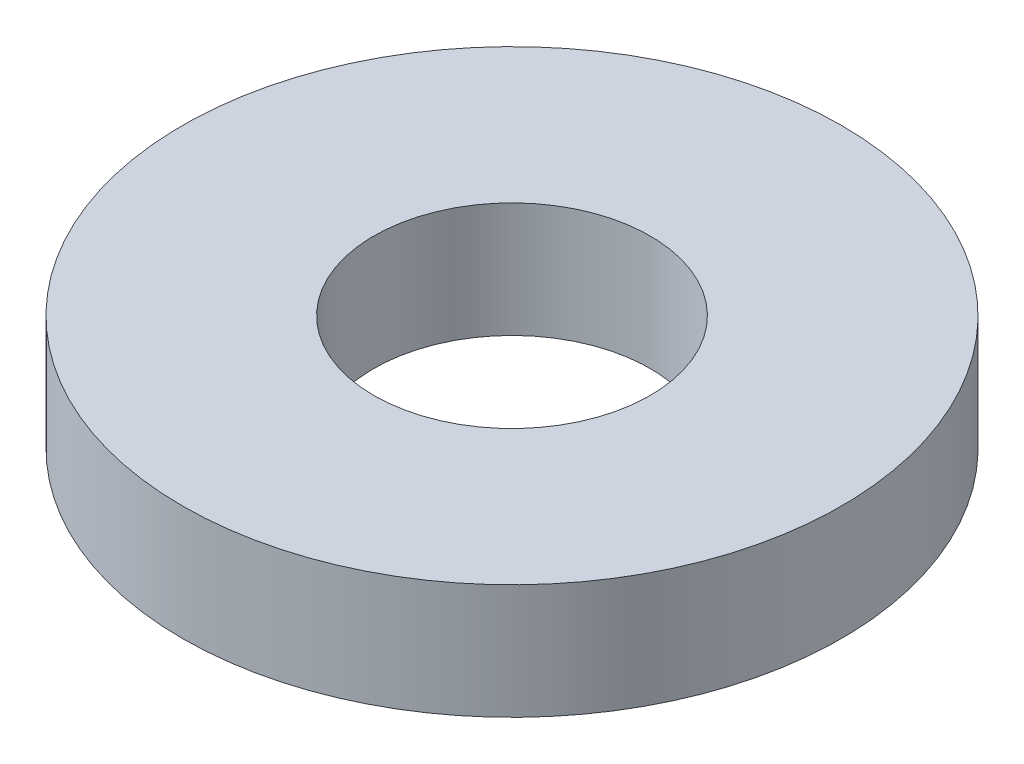
SolidWorks part; units mm, degrees
ref_plane "Front Plane" through (0, 0, 0) normal (0, 0, 1) x (1, 0, 0)
ref_plane "Top Plane" through (0, 0, 0) normal (0, 1, 0) x (1, 0, 0)
ref_plane "Right Plane" through (0, 0, 0) normal (1, 0, 0) x (0, 0, -1)
sketch "Sketch1" plane through (0, 0, 0) normal (0, 1, 0) x (1, 0, 0)
  circle A0 centre (0, 0) radius 77.5
  dimension "FLANGE_OD" = 155
extrude "Boss-Extrude1" add sketch "Sketch1" along normal blind 27
sketch "Sketch2" plane through (0, 0, 0) normal (0, 1, 0) x (1, 0, 0)
  circle A0 centre (0, 0) radius 32.5
  dimension "BORE_D" = 65
extrude "Cut-Extrude1" cut sketch "Sketch2" along normal through all
sketch "Sketch3" plane through (0, 27, 0) normal (0, 1, 0) x (1, 0, 0)
  circle A0 centre (0, 0) radius 27.1583 construction
  circle A1 centre (-27.1583, 0) radius 3.4893
  dimension "BOLT_D" = 6.9786
  dimension "BOLT_PCD" = 54.3166
extrude "Cut-Extrude2" cut sketch "Sketch3" against normal blind 26.222 rebuild error yes
pattern_circular "CirPattern1" count 8 over 360 rebuild error yes
